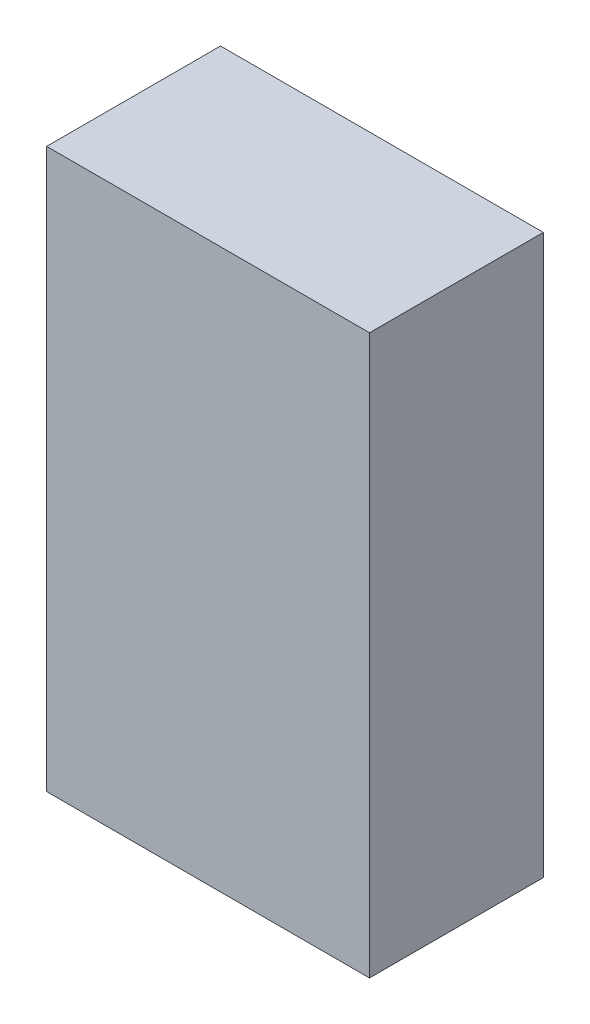
SolidWorks part; units mm, degrees
ref_plane "Front Plane" through (0, 0, 0) normal (0, 0, 1) x (1, 0, 0)
ref_plane "Top Plane" through (0, 0, 0) normal (0, 1, 0) x (1, 0, 0)
ref_plane "Right Plane" through (0, 0, 0) normal (1, 0, 0) x (0, 0, -1)
sketch "草图1" plane through (0, 0, 0) normal (0, 0, 1) x (1, 0, 0)
  line L1 (-24.8629, -22.7117) -> (1.1371, -22.7117)
  line L2 (-24.8629, -22.7117) -> (-24.8629, -67.7117)
  line L3 (-24.8629, -67.7117) -> (1.1371, -67.7117)
  line L4 (1.1371, -22.7117) -> (1.1371, -67.7117)
extrude "凸台-拉伸1" add sketch "草图1" along normal blind 14
